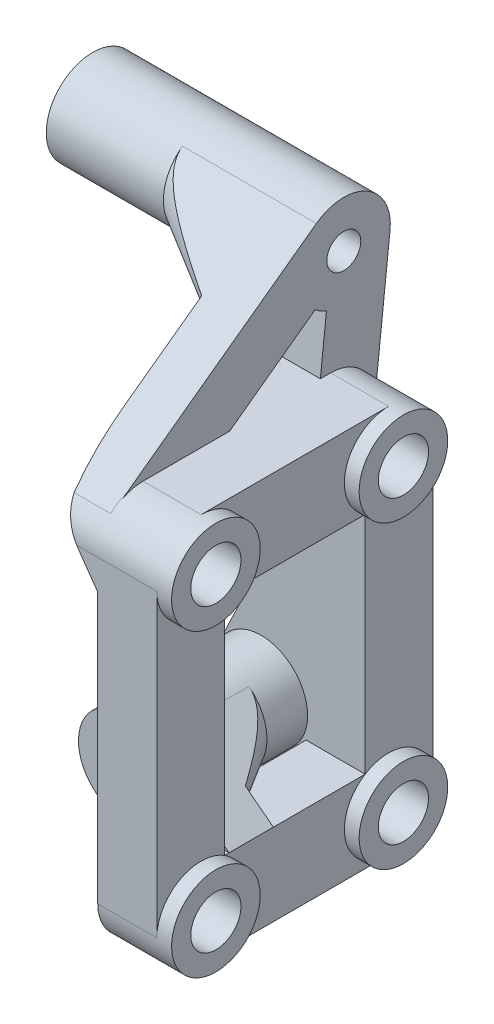
SolidWorks part; units mm, degrees
ref_plane "Ebene vorne" through (0, 0, 0) normal (0, 0, 1) x (1, 0, 0)
ref_plane "Ebene oben" through (0, 0, 0) normal (0, 1, 0) x (1, 0, 0)
ref_plane "Ebene rechts" through (0, 0, 0) normal (1, 0, 0) x (0, 0, -1)
sketch "Skizze2" plane through (74.43, 0, 0) normal (-1, 0, 0) x (0, 0, 1)
  line L0 (23.3834, -79.3) -> (18.4861, -79.3) construction
  line L1 (12.5427, -61.3936) -> (12.5427, -64.6435) construction
  circle A0 centre (18.8927, -69.14) radius 3
  circle A1 centre (18.8927, -89.46) radius 3
  circle A2 centre (6.1927, -89.46) radius 3
  circle A3 centre (6.1927, -69.14) radius 3
  dimension "D1" = 6
extrude "Aufsatz-Linear austragen1" add sketch "Skizze2" along normal blind 5
sketch "Skizze3" plane through (0, 0, 0) normal (0, 0, 1) x (1, 0, 0)
  circle A0 centre (66.3829, -85.4399) radius 3.15
  circle A1 centre (66.3829, -85.4399) radius 1.15
  dimension "D1" = 2.3
  dimension "D2" = 2
extrude "Aufsatz-Linear austragen2" add sketch "Skizze3" along normal blind 17 separate body
sketch "Skizze4" plane through (52.5, 0, 0) normal (1, 0, 0) x (0, 0, -1)
  circle A0 centre (-5.3, -59.44) radius 3.15
  circle A1 centre (-5.3, -59.44) radius 1.15
  dimension "D1" = 2.3
  dimension "D2" = 2
extrude "Aufsatz-Linear austragen3" add sketch "Skizze4" along normal blind 17 separate body
sketch "Skizze5" plane through (69.43, 0, 0) normal (-1, 0, 0) x (0, 0, 1)
  line L0 (21.8927, -69.14) -> (21.8927, -89.46)
  line L1 (18.8927, -92.46) -> (6.1927, -92.46)
  line L2 (18.8927, -66.14) -> (6.1927, -66.14)
  line L3 (3.1927, -69.14) -> (3.1927, -89.46)
  line L4 (6.1927, -69.14) -> (18.8927, -89.46) construction
  line L6 (17.3027, -86.916) -> (7.7827, -86.916)
  line L7 (17.3027, -86.916) -> (17.3027, -71.684)
  line L8 (17.3027, -71.684) -> (7.7827, -71.684)
  line L9 (7.7827, -86.916) -> (7.7827, -71.684)
  line L10 (17.3027, -86.916) -> (7.7827, -71.684) construction
  line L11 (17.3027, -71.684) -> (7.7827, -86.916) construction
  arc A0 (21.8927, -89.46) -> (18.8927, -92.46) centre (18.8927, -89.46) cw
  circle A1 centre (18.8927, -89.46) radius 3 construction
  arc A2 (21.8927, -69.14) -> (18.8927, -66.14) centre (18.8927, -69.14) ccw
  arc A3 (6.1927, -92.46) -> (3.1927, -89.46) centre (6.1927, -89.46) cw
  arc A4 (3.1927, -69.14) -> (6.1927, -66.14) centre (6.1927, -69.14) cw
  circle A5 centre (18.8927, -69.14) radius 3 construction
  circle A6 centre (6.1927, -69.14) radius 3 construction
  circle A7 centre (6.1927, -89.46) radius 3 construction
  point P21 (12.5427, -79.3)
extrude "Aufsatz-Linear austragen4" add sketch "Skizze5" against normal blind 4
sketch "Skizze6" plane through (69.43, 0, 0) normal (-1, 0, 0) x (0, 0, 1)
  line L0 (3.1927, -69.14) -> (2.1687, -59.7827)
  line L1 (7.1582, -56.8964) -> (21.014, -67.0187)
  line L2 (3.1927, -69.14) -> (21.014, -67.0187)
  circle A0 centre (5.3, -59.44) radius 3.15 construction
  arc A1 (2.1687, -59.7827) -> (7.1582, -56.8964) centre (5.3, -59.44) ccw
  arc A2 (21.8927, -69.14) -> (18.8927, -66.14) centre (18.8927, -69.14) ccw construction
extrude "Aufsatz-Linear austragen5" add sketch "Skizze6" against normal up to surface and the other way blind 3 up to face at (69.5, -59.44, 2.15)
sketch "Skizze7" plane through (0, 0, 3.1927) normal (0, 0, -1) x (-1, 0, 0)
  line L0 (-69.43, -71.684) -> (-63.5376, -84.0883)
  line L1 (-69.43, -69.14) -> (-69.43, -89.46) construction
  line L2 (-69.43, -92.46) -> (-73.43, -92.46)
  line L3 (-73.43, -92.46) -> (-73.43, -71.684)
  line L4 (-64.2657, -87.7723) -> (-69.43, -92.46)
  line L5 (-73.43, -71.684) -> (-69.43, -71.684)
  line L6 (-69.43, -92.46) -> (-69.43, -89.46) construction
  line L7 (-73.43, -92.46) -> (-69.43, -92.46) construction
  line L8 (-73.43, -69.14) -> (-73.43, -89.46) construction
  circle A0 centre (-66.3829, -85.4399) radius 3.15 construction
  arc A1 (-63.5376, -84.0883) -> (-64.2657, -87.7723) centre (-66.3829, -85.4399) ccw
extrude "Aufsatz-Linear austragen6" add sketch "Skizze7" against normal up to surface (4.59 mm away) up to face at (71.43, -79.3, 7.7827)
sketch "Skizze8" plane through (0, 0, 17) normal (0, 0, 1) x (1, 0, 0)
  line L0 (64.2657, -87.7723) -> (69.43, -92.46)
  line L2 (73.43, -86.916) -> (68.3124, -82.95)
  line L3 (73.43, -89.46) -> (73.43, -86.46) construction
  line L4 (73.43, -86.916) -> (73.43, -71.684) construction
  line L5 (73.43, -86.916) -> (69.43, -86.916)
  line L6 (69.43, -86.916) -> (69.43, -92.46)
  arc A0 (68.3124, -82.95) -> (64.2657, -87.7723) centre (66.3829, -85.4399) cw
  circle A1 centre (66.3829, -85.4399) radius 3.15 construction
extrude "Aufsatz-Linear austragen7" add sketch "Skizze8" against normal blind 3
sketch "Skizze9" plane through (74.43, 0, 0) normal (1, 0, 0) x (0, 0, -1)
  line L0 (-12.5427, -66.8316) -> (-12.5427, -79.3) construction
  line L1 (-12.5427, -79.3) -> (-1.5413, -79.3) construction
  circle A0 centre (-18.8927, -69.14) radius 1.7
  circle A1 centre (-6.1927, -69.14) radius 1.7
  circle A2 centre (-6.1927, -89.46) radius 1.7
  circle A3 centre (-18.8927, -89.46) radius 1.7
  dimension "D1" = 3.4
extrude "Schnitt-Linear austragen1" cut sketch "Skizze9" against normal blind 4
sketch "Skizze10" plane through (74.43, 0, 0) normal (1, 0, 0) x (0, 0, -1)
  line L0 (-6.1927, -92.46) -> (-3.1927, -92.46)
  line L1 (-3.1927, -92.46) -> (-3.1927, -89.46)
  arc A0 (-3.1927, -89.46) -> (-6.1927, -92.46) centre (-6.1927, -89.46) cw
  arc A1 (-6.1927, -92.46) -> (-3.1927, -89.46) centre (-6.1927, -89.46) ccw construction
  circle A2 centre (-6.1927, -89.46) radius 3 construction
  arc A3 (-7.7827, -86.916) -> (-6.1927, -92.46) centre (-6.1927, -89.46) ccw construction
extrude "Schnitt-Linear austragen2" cut sketch "Skizze10" against normal through all
sketch "Skizze11" plane through (69.5, 0, 0) normal (1, 0, 0) x (0, 0, -1)
  line L1 (-6.1927, -66.14) -> (-18.8927, -66.14) construction
  line L2 (-13.0304, -66.14) -> (-6.8883, -66.14)
  line L3 (-6.8883, -66.14) -> (-6.4749, -62.3627)
  line L5 (-2.1687, -59.7827) -> (-3.1927, -69.14) construction
  line L6 (-13.0304, -66.14) -> (-7.2478, -61.9156)
  line L7 (-20.2686, -66.4741) -> (-7.1582, -56.8964) construction
  line L8 (-12.4987, -60.7979) -> (-10.1391, -64.0278) construction
  line L9 (-6.9358, -62.2678) -> (-8.3547, -64.7208) construction
  line L10 (-2.8881, -66.3572) -> (-6.8644, -65.9221) construction
  arc A0 (-7.2478, -61.9156) -> (-6.4749, -62.3627) centre (-5.3, -59.44) ccw
  arc A1 (-7.1582, -56.8964) -> (-2.1687, -59.7827) centre (-5.3, -59.44) ccw construction
  dimension "D1" = 4
extrude "Schnitt-Linear austragen3" cut sketch "Skizze11" against normal through all
chamfer "Fase1" distance 6 angle 30 2 edges at (66.43, -62.1421, 3.681) (66.43, -59.3838, 8.4495) first distance on face at (52.5, -59.44, 2.15)
chamfer "Fase2" distance 4 angle 30 rebuild error yes
chamfer "Fase3" distance 2 angle 60 1 edges at (68.7958, -87.4648, 14) first distance on face at (69.475, -87.8236, 14)
sketch "Skizze13" plane through (0, -1.5325, -4.2056) normal (0, 0.1088, 0.9941) x (1, 0, 0)
  line L0 (69.43, -72.0749) -> (66.43, -67.841)
  line L1 (69.43, -90.2447) -> (69.43, -70.0453) construction
  line L2 (66.43, -67.841) -> (69.43, -67.841)
  line L3 (69.43, -68.0111) -> (69.43, -67.841) construction
  line L4 (69.43, -67.841) -> (69.43, -72.0749)
  line L5 (66.43, -67.841) -> (69.43, -67.841) construction
  line L6 (66.43, -68.0111) -> (66.43, -67.841) construction
  line L7 (73.43, -72.0749) -> (69.43, -72.0749) construction
extrude "Aufsatz-Linear austragen8" add sketch "Skizze13" along normal up to surface (18.8302 mm away) up to face at (71.43, -79.3, 21.8927)
sketch "Skizze14" plane through (74.43, 0, 0) normal (1, 0, 0) x (0, 0, -1)
  line L0 (-21.8927, -69.14) -> (-21.8927, -66.9225)
  line L1 (-21.8927, -66.9225) -> (-20.9133, -66.9225)
  arc A0 (-21.8927, -69.14) -> (-20.9133, -66.9225) centre (-18.8927, -69.14) cw
  circle A1 centre (-18.8927, -69.14) radius 3 construction
extrude "Schnitt-Linear austragen4" cut sketch "Skizze14" against normal through all
sketch "Skizze16" plane through (0, -0.4729, -4.3216) normal (0, -0.1088, -0.9941) x (-1, 0, 0)
  line L0 (-66.5505, -69.077) -> (-66.43, -68.9069)
  line L1 (-66.5505, -69.077) -> (-69.0036, -72.5391) construction
  line L2 (-66.43, -65.4796) -> (-66.43, -69.077) construction
  line L3 (-66.43, -68.9069) -> (-66.43, -69.077)
  line L4 (-66.43, -69.077) -> (-66.5505, -69.077)
  line L5 (-66.43, -69.077) -> (-66.5505, -69.077) construction
extrude "Schnitt-Linear austragen6" cut sketch "Skizze16" against normal through all
fillet "Verrundung1" radius 10 1 edges at (66.43, -67.9948, 12.0941)
sketch "Skizze17" plane through (73.43, 0, 0) normal (1, 0, 0) x (0, 0, -1)
  line L0 (-7.7827, -72.7258) -> (-17.3027, -71.684)
  line L1 (-7.7827, -86.916) -> (-7.7827, -71.684) construction
  line L2 (-17.3027, -71.684) -> (-7.7827, -71.684)
  line L3 (-7.7827, -71.684) -> (-7.7827, -72.7258)
  line L4 (-17.3027, -71.684) -> (-7.7827, -72.7258) construction
extrude "Schnitt-Linear austragen7" cut sketch "Skizze17" against normal through all
equation "\"M2EinschmelzGewindeDurchmesser\"=3.4"
equation "\"M2EinschmelzGewindeTiefe\"= 4.0"
equation "\"M3EinschmelzGewindeDurchmesser\"= 4.2"
equation "\"M3EinschmelzGewindeTief\"= 5.7"
equation "\"M2SchraubeLoch\"=2.3"
equation "\"M3SchraubeLoch\"=3.3"
equation "\"offSetVonGummiReifen\"= 3.0"
equation "\"D1@Skizze3\"=\"M2SchraubeLoch\""
equation "\"D1@Skizze4\"=\"M2SchraubeLoch\""
equation "\"D1@Skizze9\"=\"M2EinschmelzGewindeDurchmesser\""
equation "\"D1@Schnitt-Linear austragen1\"=\"M2EinschmelzGewindeTiefe\""
